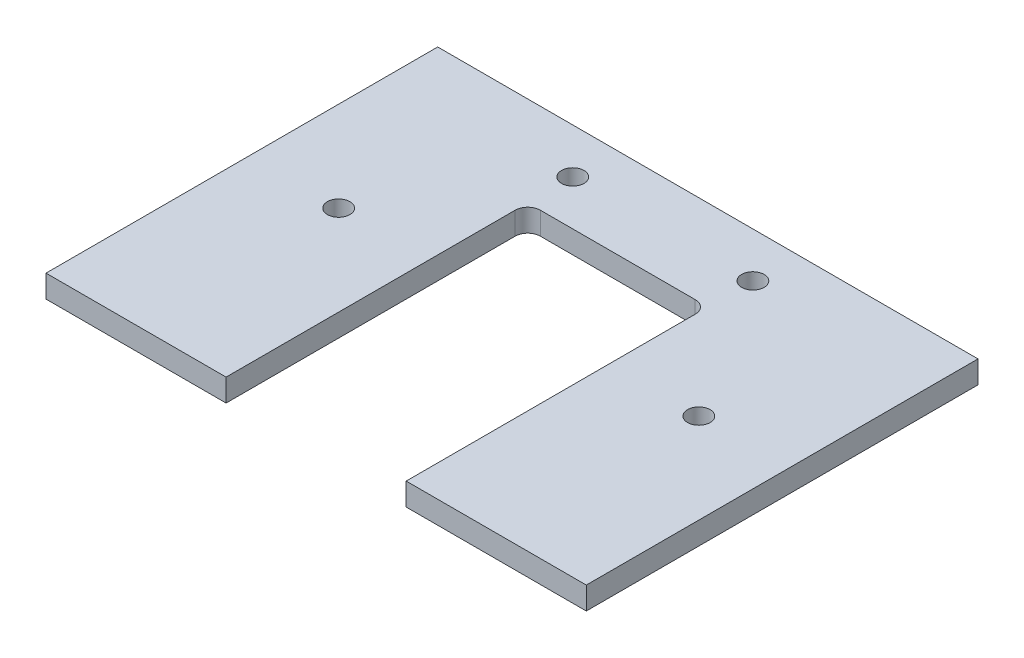
SolidWorks part; units mm, degrees
material "1060 Alloy"
ref_plane "Front Plane" through (0, 0, 0) normal (0, 0, 1) x (1, 0, 0)
ref_plane "Top Plane" through (0, 0, 0) normal (0, 1, 0) x (1, 0, 0)
ref_plane "Right Plane" through (0, 0, 0) normal (1, 0, 0) x (0, 0, -1)
sketch "Sketch1" plane through (0, 0, 0) normal (0, 1, 0) x (1, 0, 0)
  line L0 (-38.1, -42.545) -> (38.1, -42.545) construction
  line L1 (0, 0) -> (0, 12.7) construction
  line L2 (-12.7, -0.889) -> (-38.1, -0.889) construction
  line L3 (38.1, 12.7) -> (-38.1, 12.7)
  line L4 (-38.1, 12.7) -> (-38.1, -42.545)
  line L5 (-38.1, -42.545) -> (-12.7, -42.545)
  line L6 (0, 6.35) -> (-38.1, 6.35) construction
  line L7 (38.1, -0.889) -> (-38.1, -0.889) construction
  line L8 (-12.7, -42.545) -> (-12.7, 0)
  line L9 (-12.7, 0) -> (12.7, 0)
  line L10 (38.1, 12.7) -> (38.1, -42.545)
  line L11 (38.1, -42.545) -> (12.7, -42.545)
  line L12 (12.7, -42.545) -> (12.7, 0)
  line L13 (-38.1, -27.051) -> (-12.7, -27.051) construction
  line L14 (-38.1, -27.051) -> (38.1, -27.051) construction
  line L15 (-25.4, -0.889) -> (-25.4, -27.051) construction
  line L18 (38.1, 12.7) -> (-38.1, 12.7) construction
  circle A0 centre (-25.4, -13.97) radius 1.5875
  circle A2 centre (25.4, -13.97) radius 1.5875
  circle A3 centre (-12.7, 6.35) radius 1.5875
  circle A4 centre (12.7, 6.35) radius 1.5875
  dimension "D2" = 3.175
  dimension "D4" = 3.175
  dimension "D1" = 25.4
  dimension "D3" = 12.7
extrude "Boss-Extrude1" add sketch "Sketch1" along normal blind 3.175
fillet "Fillet1" radius 1.778 2 edges at (12.7, 1.5875, 0) (-12.7, 1.5875, 0)
